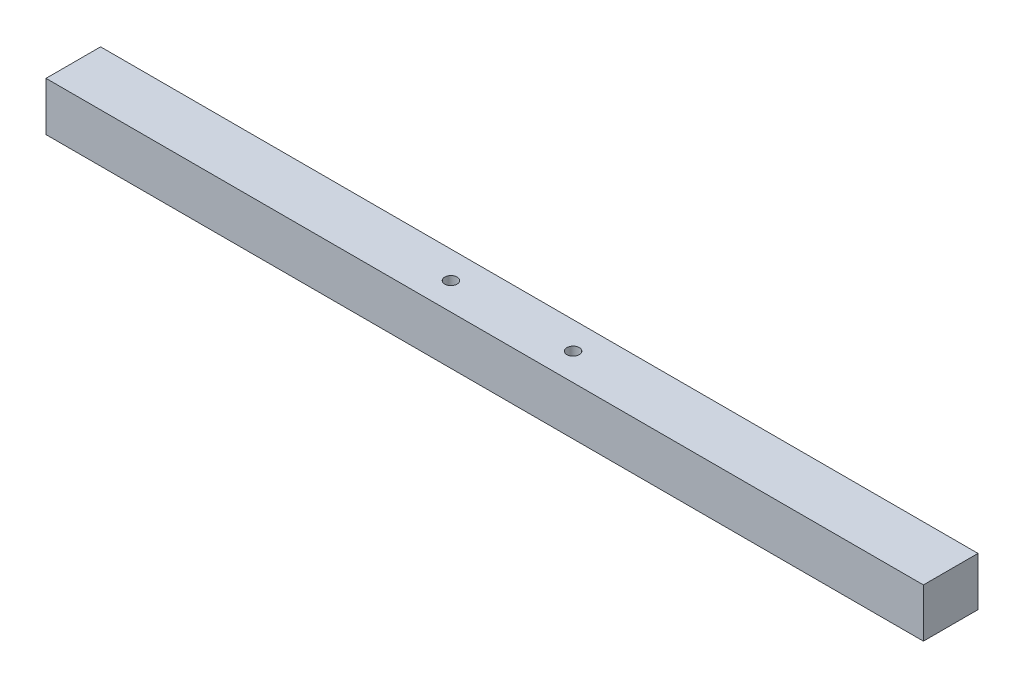
SolidWorks part; units mm, degrees
ref_plane "Alzado" through (0, 0, 0) normal (0, 0, 1) x (1, 0, 0)
ref_plane "Planta" through (0, 0, 0) normal (0, 1, 0) x (1, 0, 0)
ref_plane "Vista lateral" through (0, 0, 0) normal (1, 0, 0) x (0, 0, -1)
sketch "Croquis1" plane through (0, 0, 0) normal (0, 1, 0) x (1, 0, 0)
  line L0 (0, 0) -> (-18.8, 0) construction
  line L1 (135, -8.4) -> (-135, -8.4)
  line L2 (135, -8.4) -> (135, 8.4)
  line L3 (135, 8.4) -> (-135, 8.4)
  line L4 (-135, -8.4) -> (-135, 8.4)
  line L5 (135, -8.4) -> (-135, 8.4) construction
  line L6 (135, 8.4) -> (-135, -8.4) construction
  line L7 (0, 0) -> (18.8, 0) construction
  circle A0 centre (-18.8, 0) radius 1.9
  circle A1 centre (18.8, 0) radius 1.9
  point P0 (0, 0)
  dimension "D3" = 3.8
  dimension "D1" = 16.8
  dimension "D2" = 270
  dimension "D4" = 18.8
extrude "Saliente-Extruir1" add sketch "Croquis1" along normal blind 15
